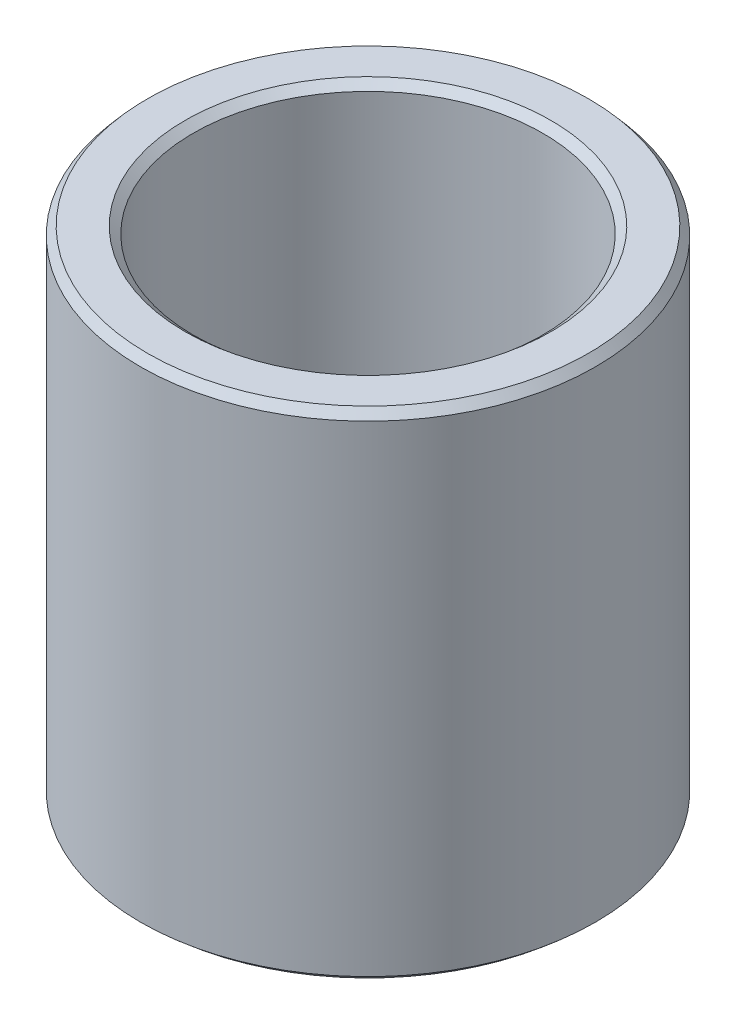
SolidWorks part; units mm, degrees
ref_plane "Front Plane" through (0, 0, 0) normal (0, 0, 1) x (1, 0, 0)
ref_plane "Top Plane" through (0, 0, 0) normal (0, 1, 0) x (1, 0, 0)
ref_plane "Right Plane" through (0, 0, 0) normal (1, 0, 0) x (0, 0, -1)
sketch "Sketch1" plane through (0, 0, 0) normal (0, 1, 0) x (1, 0, 0)
  circle A0 centre (0, 0) radius 20
  dimension "SLEEVE_OD" = 40
extrude "Boss-Extrude1" add sketch "Sketch1" along normal blind 43.6123
sketch "Sketch2" plane through (0, 0, 0) normal (0, 1, 0) x (1, 0, 0)
  circle A0 centre (0, 0) radius 15.3678
  dimension "BORE_D" = 30.7355
extrude "Cut-Extrude1" cut sketch "Sketch2" along normal through all
chamfer "Chamfer1" distance 0.7176 angle 40.577 4 edges at (0, 43.6123, 15.3678) (0, 0, 15.3678) (0, 0, 20) (0, 43.6123, 20) first distance on face at (0, 43.6123, 15.3678) first distance on face at (0, 0, 15.3678) first distance on face at (0, 43.6123, 20)
